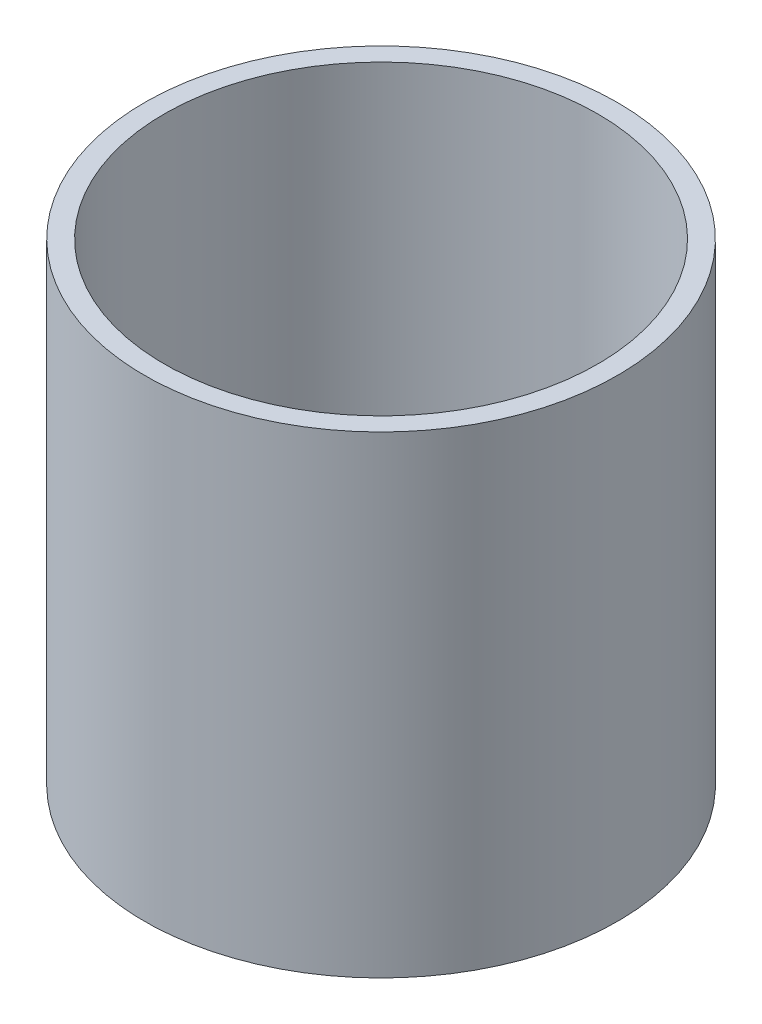
SolidWorks part; units mm, degrees
ref_plane "Спереди" through (0, 0, 0) normal (0, 0, 1) x (1, 0, 0)
ref_plane "Сверху" through (0, 0, 0) normal (0, 1, 0) x (1, 0, 0)
ref_plane "Справа" through (0, 0, 0) normal (1, 0, 0) x (0, 0, -1)
sketch "Эскиз1" plane through (0, 0, 0) normal (0, 1, 0) x (1, 0, 0)
  circle A0 centre (0, 0) radius 55
extrude "Вытянуть-Тонкостенный1" add sketch "Эскиз1" along normal blind 120 thin thin type one direction wall 5
